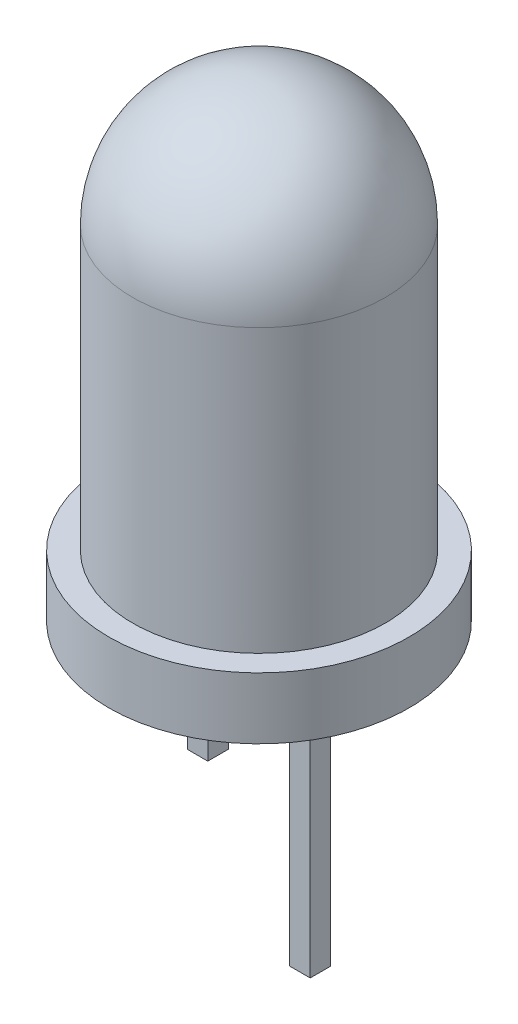
SolidWorks part; units mm, degrees
ref_plane "Front Plane" through (0, 0, 0) normal (0, 0, 1) x (1, 0, 0)
ref_plane "Top Plane" through (0, 0, 0) normal (0, 1, 0) x (1, 0, 0)
ref_plane "Right Plane" through (0, 0, 0) normal (1, 0, 0) x (0, 0, -1)
sketch "Sketch2" plane through (0, 0, 0) normal (0, 0, 1) x (1, 0, 0)
  line L0 (0, 0) -> (0, 8.7376) construction
  line L1 (0, 0) -> (2.794, 0)
  line L2 (2.794, 0) -> (2.794, 1.143)
  line L3 (2.794, 1.143) -> (2.3495, 1.143)
  line L4 (2.3495, 1.143) -> (2.3495, 6.3881)
  line L5 (0, 0) -> (0, 8.7376)
  arc A0 (2.3495, 6.3881) -> (0, 8.7376) centre (0, 6.3881) ccw
  dimension "D5" = 4.699
  dimension "D1" = 8.7376
  dimension "D2" = 5.588
  dimension "D3" = 1.143
  dimension "D4" = 4.699
revolve "Revolve1" add sketch "Sketch2" angle 360 about L0
sketch "Sketch3" plane through (0, 0, 0) normal (0, -1, 0) x (1, 0, 0)
  line L0 (0, 0) -> (0, 2.794) construction
  line L1 (-1.143, 0.1905) -> (-0.762, 0.1905)
  line L2 (-1.143, 0.1905) -> (-1.143, -0.1905)
  line L3 (-1.143, -0.1905) -> (-0.762, -0.1905)
  line L4 (-0.762, 0.1905) -> (-0.762, -0.1905)
  line L5 (-1.143, 0.1905) -> (-0.762, -0.1905) construction
  line L6 (-1.143, -0.1905) -> (-0.762, 0.1905) construction
  line L7 (0.762, 0.1905) -> (1.143, 0.1905)
  line L8 (0.762, 0.1905) -> (0.762, -0.1905)
  line L9 (0.762, -0.1905) -> (1.143, -0.1905)
  line L10 (1.143, 0.1905) -> (1.143, -0.1905)
  line L11 (0.762, 0.1905) -> (1.143, -0.1905) construction
  line L12 (0.762, -0.1905) -> (1.143, 0.1905) construction
  circle A0 centre (0, 0) radius 2.794 construction
  point P0 (-0.9525, 0)
  point P5 (0.9525, 0)
  dimension "D1" = 0.381
  dimension "D2" = 0.381
  dimension "D3" = 1.905
extrude "Boss-Extrude1" add sketch "Sketch3" along normal blind 5.08 contours L10 L7 L8 L9 region at (0.9525, 0, 0)
extrude "Boss-Extrude2" add sketch "Sketch3<4>" along normal blind 2.54 contours L4 L1 L2 L3 region at (-0.9525, 0, 0)
sketch "Sketch3<4>" plane through (0, 0, 0) normal (0, -1, 0) x (1, 0, 0) same geometry as "Sketch3"
scale "Echelle1" bodies to scale 103 scale about centroid uniform scaling yes scale factor 4
